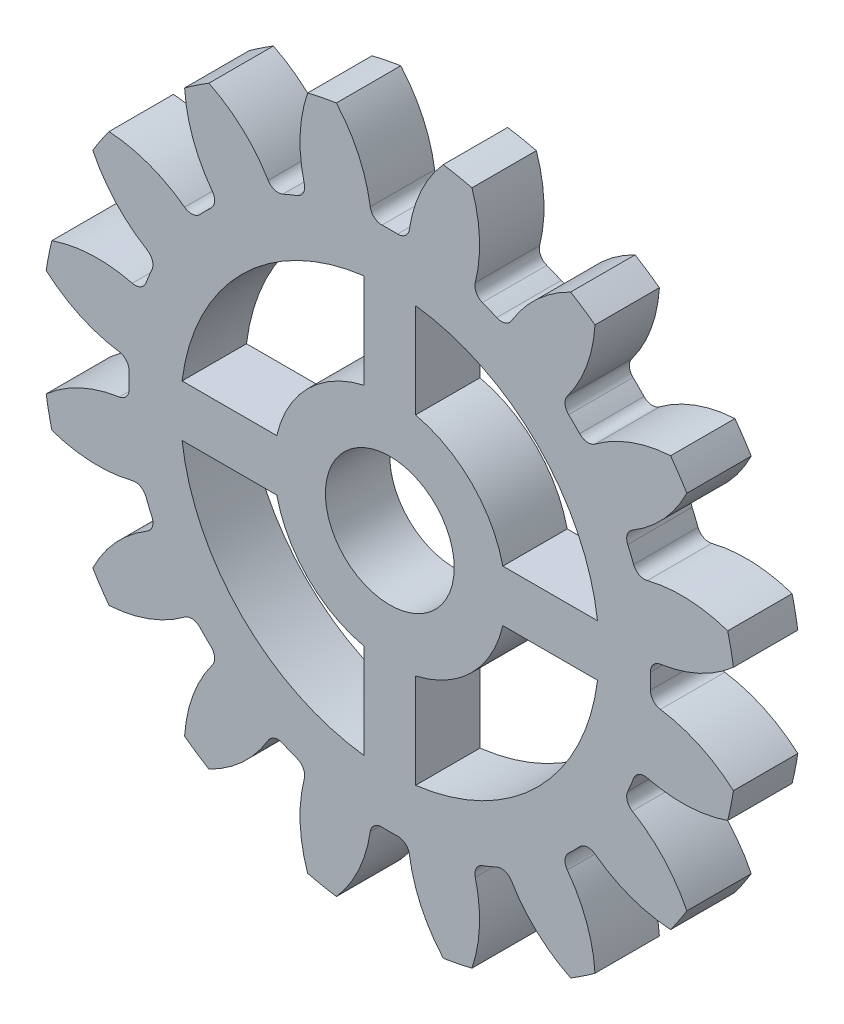
SolidWorks part; units mm, degrees
material "6061-T6 (SS)"
ref_plane "Front Plane" through (0, 0, 0) normal (0, 0, 1) x (1, 0, 0)
ref_plane "Top Plane" through (0, 0, 0) normal (0, 1, 0) x (1, 0, 0)
ref_plane "Right Plane" through (0, 0, 0) normal (1, 0, 0) x (0, 0, -1)
sketch "Sketch1" plane through (0, 0, 0) normal (0, 0, 1) x (1, 0, 0)
  circle A0 centre (0, 0) radius 24
  circle A1 centre (0, 0) radius 27
  circle A2 centre (0, 0) radius 20.25
  dimension "D1" = 48
  dimension "D2" = 54
  dimension "D3" = 6.75
extrude "Boss-Extrude1" add sketch "Sketch1" along normal mid plane 5 contours A1
sketch "Sketch2" plane through (0, 0, 0) normal (0, 0, 1) x (1, 0, 0)
  line L0 (0, 0) -> (0, 27) construction
  line L1 (-2.3524, 23.8844) -> (2.3524, 23.8844) construction
  line L2 (-1.4318, 20.1993) -> (0, 0) construction
  line L3 (0, 18.6008) -> (-4.0535, 27.705) construction
  line L4 (0, 0) -> (5.2674, 26.4812) construction
  line L5 (2.3524, 23.8844) -> (6.9668, 22.9666) construction
  circle A0 centre (0, 0) radius 27 construction
  arc A1 (-5.0055, 27.549) -> (-1.4318, 20.1993) centre (-12.3708, 19.4239) cw
  arc A2 (5.0055, 27.549) -> (1.4318, 20.1993) centre (12.3708, 19.4239) ccw
  circle A3 centre (0, 0) radius 20.25 construction
  arc A4 (1.4318, 20.1993) -> (-1.4318, 20.1993) centre (0, 0) ccw
  circle A6 centre (0, 0) radius 24 construction
  circle A7 centre (0, 0) radius 28
  arc A8 (5.0055, 27.549) -> (-5.0055, 27.549) centre (0, 0) ccw
  circle A9 centre (0, 0) radius 27 construction
  dimension "D2" = 24
  dimension "D3" = 11.25
extrude "Cut-Extrude1" cut sketch "Sketch2" against normal through all both and the other way through all
fillet "Fillet1" radius 0.9 2 edges at (1.4318, 20.1993, 0) (-1.4318, 20.1993, 0)
pattern_circular "CirPattern1" count 16 over 360 about axis through (0, 0, 2.5) along (0, 0, 1) of "Cut-Extrude1", "Fillet1"
sketch "Sketch3" plane through (0, 0, 2.5) normal (0, 0, 1) x (1, 0, 0)
  line L0 (0, 0) -> (0, 16.25) construction
  line L1 (-2, 16.1265) -> (-2, 8.775)
  line L2 (2, 16.1265) -> (2, 8.775)
  line L3 (16.1265, 2) -> (8.775, 2)
  line L4 (16.1265, -2) -> (8.775, -2)
  line L5 (2, -16.1265) -> (2, -8.775)
  line L6 (-2, -16.1265) -> (-2, -8.775)
  line L7 (-16.1265, -2) -> (-8.775, -2)
  line L8 (-16.1265, 2) -> (-8.775, 2)
  circle A0 centre (0, 0) radius 5
  arc A2 (-2, 8.775) -> (-8.775, 2) centre (0, 0) ccw
  circle A3 centre (0, 0) radius 16.25
  arc A4 (-2, 16.1265) -> (-16.1265, 2) centre (0, 0) ccw
  arc A5 (16.1265, 2) -> (2, 16.1265) centre (0, 0) ccw
  circle A6 centre (0, 0) radius 9 construction
  arc A7 (8.775, 2) -> (2, 8.775) centre (0, 0) ccw
  arc A8 (2, -16.1265) -> (16.1265, -2) centre (0, 0) ccw
  arc A9 (2, -8.775) -> (8.775, -2) centre (0, 0) ccw
  arc A10 (-8.775, -2) -> (-2, -8.775) centre (0, 0) ccw
  arc A11 (-16.1265, -2) -> (-2, -16.1265) centre (0, 0) ccw
  point P9 (9, 0)
  point P28 (0, 0)
  dimension "D1" = 10
  dimension "D4" = 4
  dimension "D2" = 4
  dimension "D3" = 4
  dimension "D5" = 4
extrude "Cut-Extrude2" cut sketch "Sketch3" against normal through all both
equation "\"Module\"= 3mm"
equation "\"Number of Teeth\"= 16"
equation "\"D1@Sketch1\"=\"Module\" * \"Number of Teeth\""
equation "\"D2@Sketch1\"=(\"Number of Teeth\" + 2) * \"Module\""
equation "\"D3@Sketch1\"=\"Module\" * if( \"Module\"=>1.25,2.25,2.4)"
equation "\"Pressure Angle\"= 24deg"
equation "\"D2@Sketch2\"=\"Pressure Angle\""
equation "\"D3@Sketch2\"=180 / \"Number of Teeth\""
equation "\"D1@Fillet1\"=0.3 * \"Module\""
equation "\"D1@CirPattern1\"=\"Number of Teeth\""
